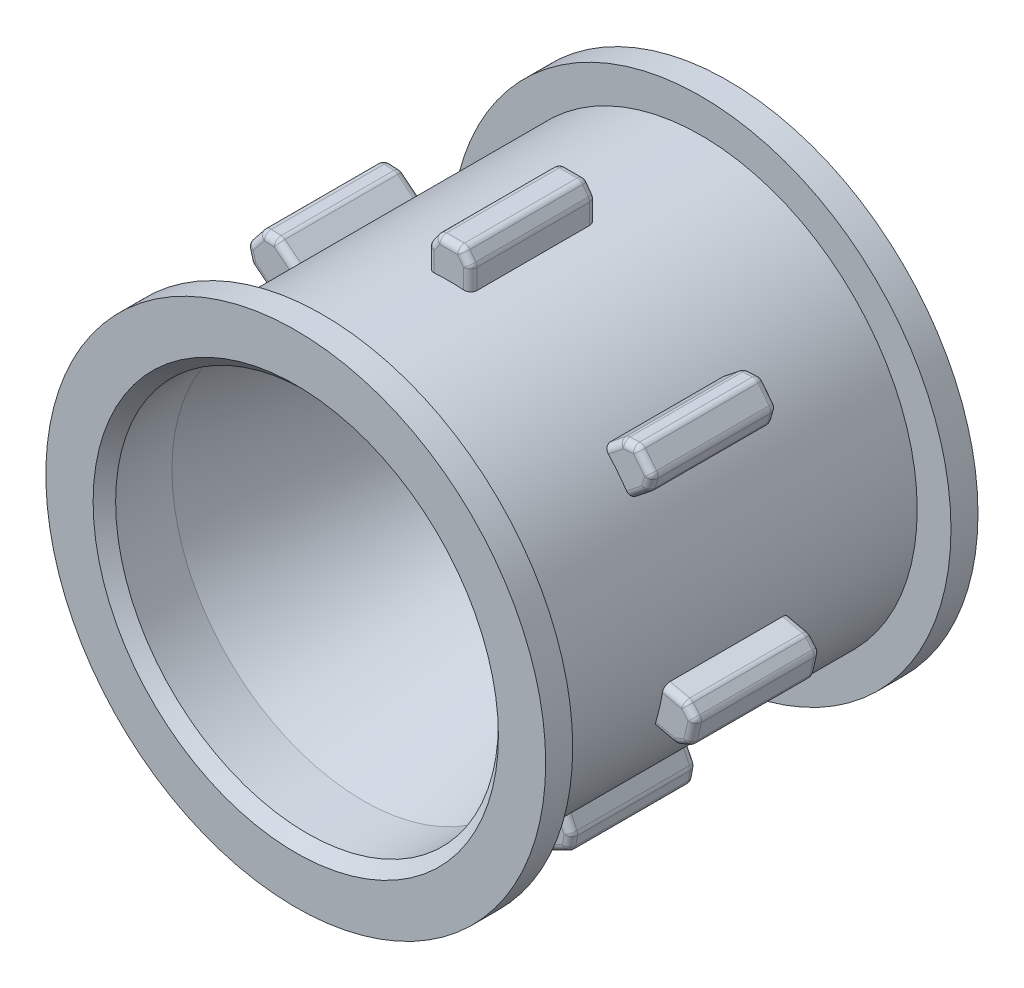
SolidWorks part; units mm, degrees
ref_plane "Ebene vorne" through (0, 0, 0) normal (0, 0, 1) x (1, 0, 0)
ref_plane "Ebene oben" through (0, 0, 0) normal (0, 1, 0) x (1, 0, 0)
ref_plane "Ebene rechts" through (0, 0, 0) normal (1, 0, 0) x (0, 0, -1)
sketch "Skizze1" plane through (0, 0, 0) normal (0, 0, 1) x (1, 0, 0)
  circle A0 centre (0, 0) radius 9.6
  dimension "D1" = 19.2
extrude "Laufrad" add sketch "Skizze1" along normal blind 8.4 and the other way blind 8.4
sketch "Skizze2" plane through (0, 0, 8.4) normal (0, 0, 1) x (1, 0, 0)
  circle A0 centre (0, 0) radius 11.1
  circle A1 centre (0, 0) radius 9.6 construction
  dimension "D1" = 1.5
extrude "Kettenführung" add sketch "Skizze2" along normal blind 1.2
mirror "Spiegeln Kettenführung" about plane through (0, 0, 0) normal (0, 0, 1) of "Kettenführung"
sketch "Skizze4" plane through (0, 0, -9.6) normal (0, 0, -1) x (-1, 0, 0)
  circle A0 centre (0, 0) radius 1
  dimension "D1" = 2
extrude "SchraubenBohrung M3" cut sketch "Skizze4" against normal through all
sketch "Skizze3" plane through (0, 0, -9.6) normal (0, 0, -1) x (-1, 0, 0)
  circle A0 centre (0, 0) radius 4.1
  dimension "D1" = 8.2
extrude "Kugellagersitz" cut sketch "Skizze3" against normal blind 4
sketch "Skizze5" plane through (0, 0, 0) normal (1, 0, 0) x (0, 0, -1)
  line L0 (-9.6, 0) -> (-9.6, 8.5)
  line L1 (-9.6, 8.5) -> (-6.6, 8.5)
  line L2 (-6.6, 8.5) -> (4.1, 6)
  line L3 (4.1, 6) -> (4.1, 0)
  line L4 (9.6, -4.1) -> (9.6, 4.1) construction
  line L5 (-9.6, 0) -> (5.6, 0) construction
  line L6 (-9.6, 0) -> (4.1, 0)
  line L7 (-9.6, 11.1) -> (-9.6, -11.1) construction
  dimension "D1" = 5.5
  dimension "D2" = 3
  dimension "D3" = 8.5
  dimension "D4" = 6
revolve "Schnitt-Rotation3" cut sketch "Skizze5" angle 360 about axis through (0, 0, -8.4) along (0, 0, 1)
chamfer "Fase1" distance 0.5 angle 45 5 edges at (-1, 0, -4.1) (-1, 0, -5.6) (-4.1, 0, -9.6) (-8.5, 0, 9.6) (-6, 0, -4.1) first distance on face at (-6, 0, -4.1) first distance on face at (-1, 0, -4.1) first distance on face at (-4.1, 0, -9.6) first distance on face at (-8.5, 0, 9.6)
sketch "Skizze6" plane through (0, 0, 0) normal (0, 0, 1) x (1, 0, 0)
  line L0 (0, 0) -> (0, 10.3) construction
  line L1 (0, 10.3) -> (0, 11.1) construction
  line L2 (0.55, 11.1) -> (-0.55, 11.1)
  line L3 (-0.55, 11.1) -> (-0.95, 10.5424)
  line L4 (-0.95, 10.5424) -> (-0.95, 9.5529)
  line L5 (0.95, 10.5424) -> (0.95, 9.5529)
  line L6 (0.55, 11.1) -> (0.95, 10.5424)
  line L7 (-0.95, 9.5529) -> (0.95, 9.5529)
  circle A1 centre (0, 0) radius 9.6 construction
  dimension "D1" = 0.8
  dimension "D2" = 10.3
  dimension "D3" = 1.9
  dimension "D4" = 1.1
extrude "Zahn" add sketch "Skizze6" along normal blind 2.8 and the other way blind 2.8
fillet "Verrundung1" radius 0.3 14 edges at (0.95, 10.5424, 0) (-0.95, 10.5424, 0) (-0.95, 10.0476, -2.8) (-0.75, 10.8212, -2.8) (0, 11.1, -2.8) (0.75, 10.8212, -2.8) (0.95, 10.0476, -2.8) (-0.55, 11.1, 0) (0.55, 11.1, 0) (-0.95, 10.0476, 2.8) (-0.75, 10.8212, 2.8) (0, 11.1, 2.8) (0.75, 10.8212, 2.8) (0.95, 10.0476, 2.8)
pattern_circular "Kreismuster1" count 7 over 360 about axis through (0, 0, -8.4) along (0, 0, 1) of "Zahn", "Verrundung1"
sketch "Skizze8" plane through (0, 0, -9.6) normal (0, 0, -1) x (-1, 0, 0)
  line L0 (0, 11.1) -> (0, -11.1) construction
  line L1 (0, -11.1) -> (0, 11.1) construction
  line L2 (11.1, 0) -> (-11.1, 0) construction
  line L3 (2, 8.5) -> (2, -8.5)
  line L4 (2, -8.5) -> (-2, -8.5)
  line L5 (-2, -8.5) -> (-2, 8.5)
  line L6 (-2, 0) -> (2, 0)
  line L7 (2, 8.5) -> (-2, 8.5)
  circle A0 centre (0, 0) radius 11.1 construction
  point P12 (0, 0)
  circle M6 centre (0, 0) radius 4.6
  dimension "D1" = 8.5
  dimension "D2" = 2
  dimension "D3" = 2
extrude "Auschnitt Antrieb Wage" cut sketch "Skizze8" against normal blind 2 contours L5 L6 L3 M6 | L3 L7 L5 M6 | L6 L5 L3 M6 | L5 L4 L3 M6 region at (0, 6.4731, -9.6) region at (0, 2.2274, -9.6) region at (0, -2.2274, -9.6) region at (0, -6.4731, -9.6)
sketch "Skizze10" plane through (0, 0, -9.6) normal (0, 0, -1) x (-1, 0, 0)
  line L0 (0, 11.1) -> (0, -11.1) construction
  line L1 (0, 10.56) -> (0, -10.56) construction
  line L2 (-8.5, 3.5) -> (8.5, 3.5)
  line L3 (8.5, 3.5) -> (8.5, -3.5)
  line L4 (8.5, -3.5) -> (-8.5, -3.5)
  line L5 (0, -3.5) -> (0, 3.5)
  line L6 (10.56, 0) -> (-10.56, 0) construction
  line L7 (-8.5, 3.5) -> (-8.5, -3.5)
  circle A0 centre (0, 0) radius 11.1 construction
  arc M7 (-2, -4.1425) -> (-2, 4.1425) centre (0, 0) cw
  arc M11 (2, 4.1425) -> (2, -4.1425) centre (0, 0) cw
  dimension "D1" = 8.5
  dimension "D2" = 3.5
  dimension "D3" = 3.5
extrude "Schnitt-Linear austragen2" cut sketch "Skizze10" against normal blind 2 contours L4 L3 L2 M11 | L2 L7 L4 M7 | L4 L5 L2 M7 | L5 L4 L2 M11 region at (6.2785, 0, -9.6) region at (2.0794, 0, -9.6) region at (-2.0794, 0, -9.6) region at (-6.2785, 0, -9.6)
